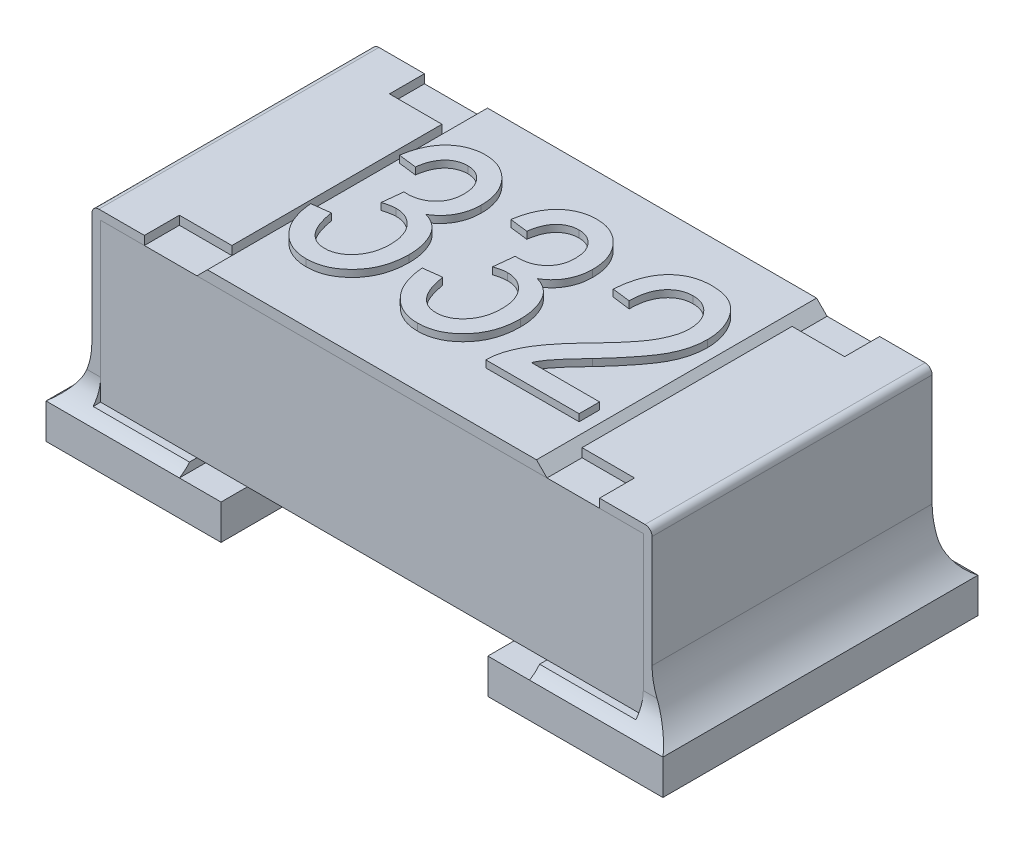
SolidWorks part; units mm, degrees
material "Ceramic Porcelain"
ref_plane "Front Plane" through (0, 0, 0) normal (0, 0, 1) x (1, 0, 0)
ref_plane "Top Plane" through (0, 0, 0) normal (0, 1, 0) x (1, 0, 0)
ref_plane "Right Plane" through (0, 0, 0) normal (1, 0, 0) x (0, 0, -1)
sketch "Sketch1" plane through (0, 0, 0) normal (1, 0, 0) x (0, 0, -1)
  line L0 (0, 55) -> (0, -55) construction
  line L1 (-0.4, 0.575) -> (0.4, 0.575)
  line L2 (-0.4, 0.575) -> (-0.4, 0.125)
  line L3 (-0.4, 0.125) -> (0.4, 0.125)
  line L4 (0.4, 0.575) -> (0.4, 0.125)
  line L5 (55, 0) -> (-55, 0) construction
  dimension "D1" = 0.8
  dimension "D2" = 0.4
  dimension "D3" = 0.45
  dimension "D4" = 0.125
extrude "Boss-Extrude1" add sketch "Sketch1" along normal mid plane 1.55
sketch "Sketch2" plane through (0, 0, 0) normal (0, 0, 1) x (1, 0, 0)
  line L0 (-0.5, 0.6) -> (-0.78, 0.6)
  line L1 (-0.8, 0.58) -> (-0.8, 0.1)
  line L2 (-0.8, 0.1) -> (-0.5, 0.1)
  line L3 (-0.5, 0.1) -> (-0.5, 0.125)
  line L4 (0.775, 0.125) -> (-0.775, 0.125) construction
  line L5 (-0.5, 0.125) -> (-0.775, 0.125)
  line L6 (-0.775, 0.125) -> (-0.775, 0.575)
  line L7 (-0.775, 0.575) -> (-0.5, 0.575)
  line L8 (0.775, 0.575) -> (-0.775, 0.575) construction
  line L9 (-0.5, 0.575) -> (-0.5, 0.6)
  line L11 (0.5, 0.575) -> (0.5, 0.6)
  line L12 (0.5, 0.6) -> (0.78, 0.6)
  line L13 (0.8, 0.58) -> (0.8, 0.1)
  line L14 (0.8, 0.1) -> (0.5, 0.1)
  line L15 (0.5, 0.1) -> (0.5, 0.125)
  line L16 (0.5, 0.125) -> (0.775, 0.125)
  line L17 (0.775, 0.125) -> (0.775, 0.575)
  line L18 (0.775, 0.575) -> (0.5, 0.575)
  arc A0 (0.78, 0.6) -> (0.8, 0.58) centre (0.78, 0.58) cw
  arc A1 (-0.78, 0.6) -> (-0.8, 0.58) centre (-0.78, 0.58) ccw
  point P28 (-0.8, 0.6)
  dimension "D6" = 0.02
  dimension "D1" = 0.025
  dimension "D2" = 0.025
  dimension "D3" = 0.025
  dimension "D4" = 0.3
  dimension "D5" = 0.3
extrude "Boss-Extrude2" add sketch "Sketch2" along normal mid plane 0.8 separate body
sketch "Sketch3" plane through (0, 0.6, 0) normal (0, 1, 0) x (1, 0, 0)
  line L0 (0.5, -0.4) -> (0.5, 0.4) construction
  line L1 (-0.5, 0.4) -> (-0.65, 0.4)
  line L2 (-0.5, 0.4) -> (-0.5, 0.3)
  line L3 (-0.5, 0.3) -> (-0.65, 0.3)
  line L4 (-0.65, 0.4) -> (-0.65, 0.3)
  line L5 (-0.5, -0.4) -> (-0.65, -0.4)
  line L6 (-0.5, -0.4) -> (-0.5, -0.3)
  line L7 (-0.5, -0.3) -> (-0.65, -0.3)
  line L8 (-0.65, -0.4) -> (-0.65, -0.3)
  line L9 (0.5, -0.4) -> (0.65, -0.4)
  line L10 (0.5, -0.4) -> (0.5, -0.3)
  line L11 (0.5, -0.3) -> (0.65, -0.3)
  line L12 (0.65, -0.4) -> (0.65, -0.3)
  line L13 (0.775, -0.4) -> (-0.775, -0.4) construction
  line L15 (0.5, 0.4) -> (0.65, 0.4)
  line L16 (0.5, 0.4) -> (0.5, 0.3)
  line L17 (0.5, 0.3) -> (0.65, 0.3)
  line L18 (0.65, 0.4) -> (0.65, 0.3)
  dimension "D1" = 0.15
  dimension "D2" = 0.1
extrude "Cut-Extrude1" cut sketch "Sketch3" against normal blind 0.025
sketch "Sketch4" plane through (0, 0, 0) normal (0, 0, 1) x (1, 0, 0)
  line L0 (-0.5, 0.575) -> (0.5, 0.575)
  line L1 (0.5, 0.575) -> (0.47, 0.605)
  line L2 (0.47, 0.605) -> (-0.47, 0.605)
  line L3 (-0.47, 0.605) -> (-0.5, 0.575)
  dimension "D1" = 45
  dimension "D2" = 45
  dimension "D3" = 0.03
extrude "Boss-Extrude3" add sketch "Sketch4" along normal mid plane 0.8 separate body
sketch "Sketch7" plane through (0, 0, 0) normal (0, 1, 0) x (1, 0, 0)
  line L0 (0, -0.2777) -> (0, 0.2777) construction
  line L1 (-0.381, -0.45) -> (-0.881, -0.45)
  line L2 (-0.381, -0.45) -> (-0.381, 0.45)
  line L3 (-0.381, 0.45) -> (-0.881, 0.45)
  line L4 (-0.881, -0.45) -> (-0.881, 0.45)
  line L5 (0.381, -0.45) -> (0.881, -0.45)
  line L6 (0.381, -0.45) -> (0.381, 0.45)
  line L7 (0.381, 0.45) -> (0.881, 0.45)
  line L8 (0.881, -0.45) -> (0.881, 0.45)
  line L9 (-0.2777, 0) -> (0.2777, 0) construction
  dimension "D1" = 0.5
  dimension "D2" = 0.381
  dimension "D3" = 0.381
  dimension "D4" = 0.9
  dimension "D5" = 0.45
extrude "Boss-Extrude5" add sketch "Sketch7" along normal blind 0.1
fillet "Fillet3" radius 0.2 1 edges at (-0.8, 0.1, 0)
fillet "Fillet4" radius 0.2 1 edges at (0.8, 0.1, 0)
fillet "Fillet5" radius 0.1 2 edges at (0.6905, 0.1, -0.4) (0.6905, 0.1, 0.4)
fillet "Fillet6" radius 0.1 2 edges at (-0.6905, 0.1, 0.4) (-0.6905, 0.1, -0.4)
sketch "Esquisse2" plane through (0, 0.605, 0) normal (0, 1, 0) x (1, 0, 0)
  text T0 "332" font "Arial Narrow" height 0.5
extrude "Boss.-Extru.1" add sketch "Esquisse2" along normal blind 0.02
